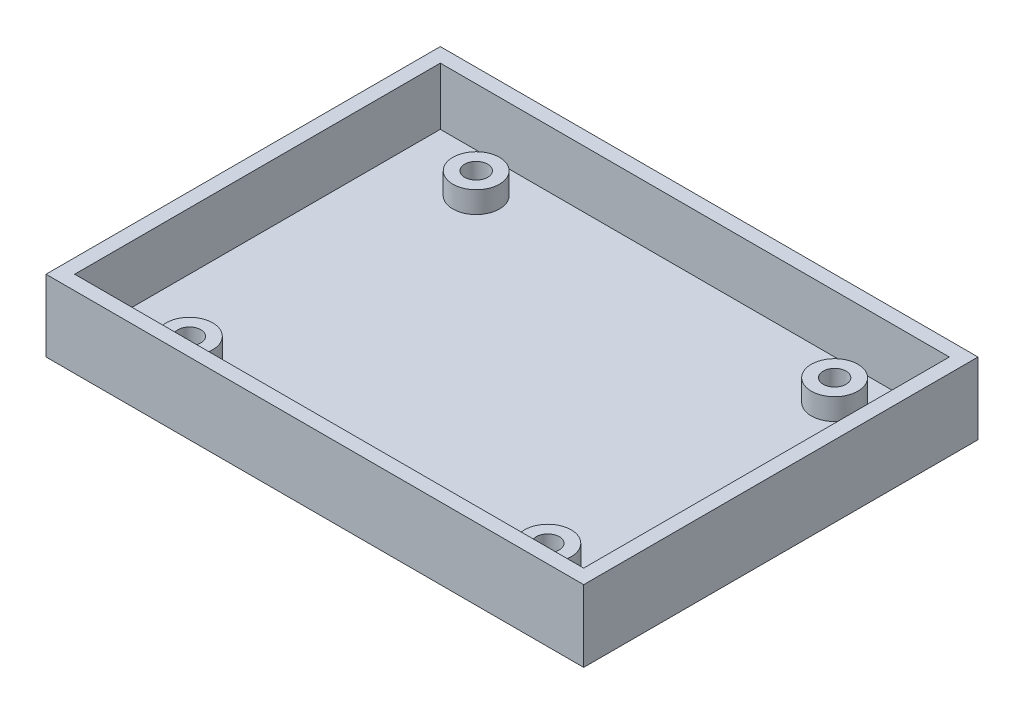
SolidWorks part; units mm, degrees
ref_plane "Front Plane" through (0, 0, 0) normal (0, 0, 1) x (1, 0, 0)
ref_plane "Top Plane" through (0, 0, 0) normal (0, 1, 0) x (1, 0, 0)
ref_plane "Right Plane" through (0, 0, 0) normal (1, 0, 0) x (0, 0, -1)
sketch "Sketch1" plane through (0, 0, 0) normal (0, 1, 0) x (1, 0, 0)
  line L1 (37.5, -27.5) -> (-37.5, -27.5)
  line L2 (37.5, -27.5) -> (37.5, 27.5)
  line L3 (37.5, 27.5) -> (-37.5, 27.5)
  line L4 (-37.5, -27.5) -> (-37.5, 27.5)
  line L5 (37.5, -27.5) -> (-37.5, 27.5) construction
  line L6 (37.5, 27.5) -> (-37.5, -27.5) construction
  point P0 (0, 0)
  dimension "D1" = 75
  dimension "D2" = 55
extrude "Body" add sketch "Sketch1" along normal blind 10
shell "Shell1" thickness 2 removed face at (0, 10, 0)
sketch "Sketch2" plane through (0, 2, 0) normal (0, 1, 0) x (1, 0, 0)
  line L1 (25, -20) -> (-25, -20) construction
  line L2 (25, -20) -> (25, 20) construction
  line L3 (25, 20) -> (-25, 20) construction
  line L4 (-25, -20) -> (-25, 20) construction
  line L5 (25, -20) -> (-25, 20) construction
  line L6 (25, 20) -> (-25, -20) construction
  circle A0 centre (-25, 20) radius 3.25
  circle A1 centre (25, 20) radius 3.25
  circle A2 centre (25, -20) radius 3.25
  circle A3 centre (-25, -20) radius 3.25
  point P0 (0, 0)
  dimension "D3" = 6.5
  dimension "D1" = 50
  dimension "D2" = 40
extrude "Inserts_Support" add sketch "Sketch2" along normal blind 3
sketch "Sketch3" plane through (0, 5, 0) normal (0, 1, 0) x (1, 0, 0)
  circle A0 centre (-25, 20) radius 1.6
  circle A1 centre (25, 20) radius 1.6
  circle A2 centre (25, -20) radius 1.6
  circle A3 centre (-25, -20) radius 1.6
  dimension "D1" = 3.2
extrude "Inserts_Holes" cut sketch "Sketch3" against normal blind 4
